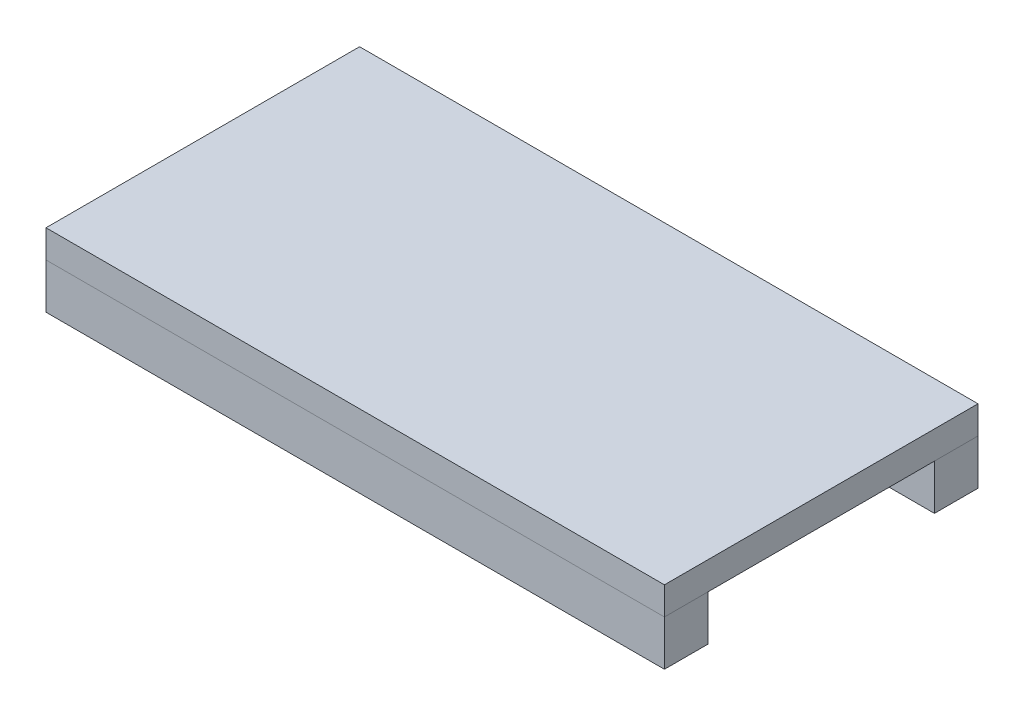
SolidWorks part; units mm, degrees
ref_plane "Front Plane" through (0, 0, 0) normal (0, 0, 1) x (1, 0, 0)
ref_plane "Top Plane" through (0, 0, 0) normal (0, 1, 0) x (1, 0, 0)
ref_plane "Right Plane" through (0, 0, 0) normal (1, 0, 0) x (0, 0, -1)
sketch "Sketch1" plane through (0, 0, 0) normal (0, 1, 0) x (1, 0, 0)
  line L1 (17.75, 9) -> (-17.75, 9)
  line L2 (17.75, 9) -> (17.75, -9)
  line L3 (17.75, -9) -> (-17.75, -9)
  line L4 (-17.75, 9) -> (-17.75, -9)
  line L5 (17.75, 9) -> (-17.75, -9) construction
  line L6 (17.75, -9) -> (-17.75, 9) construction
  point P0 (0, 0)
  dimension "D1" = 18
  dimension "D2" = 35.5
extrude "Boss-Extrude1" add sketch "Sketch1" along normal blind 1.6
sketch "Sketch2" plane through (0, 0, 0) normal (0, -1, 0) x (1, 0, 0)
  line L0 (17.75, 9) -> (17.75, -9) construction
  line L1 (-17.75, 9) -> (17.75, 9)
  line L2 (-17.75, 9) -> (-17.75, 6.5)
  line L3 (-17.75, 6.5) -> (17.75, 6.5)
  line L4 (17.75, 9) -> (17.75, 6.5)
  line L5 (-17.75, 0) -> (17.75, 0) construction
  line L6 (-17.75, -9) -> (-17.75, 9) construction
  line L7 (17.75, -9) -> (17.75, -6.5)
  line L8 (-17.75, -6.5) -> (17.75, -6.5)
  line L9 (-17.75, -9) -> (-17.75, -6.5)
  line L10 (-17.75, -9) -> (17.75, -9)
  dimension "D1" = 2.5
extrude "Boss-Extrude2" add sketch "Sketch2" along normal blind 2.6
